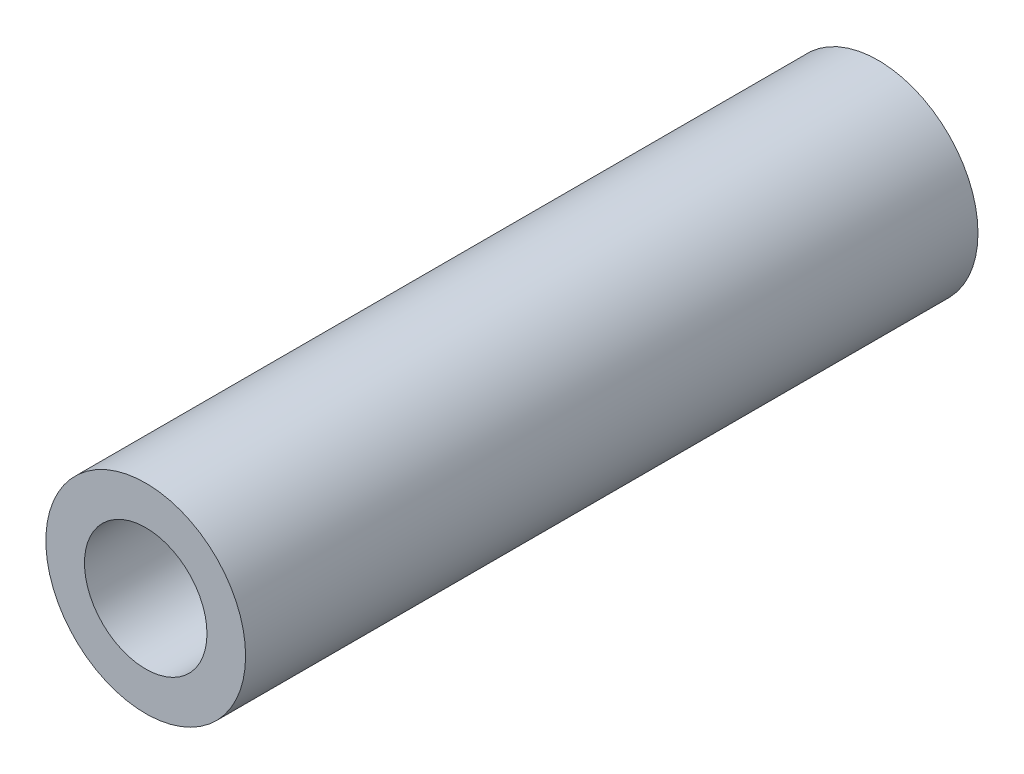
SolidWorks part; units mm, degrees
ref_plane "Front Plane" through (0, 0, 0) normal (0, 0, 1) x (1, 0, 0)
ref_plane "Top Plane" through (0, 0, 0) normal (0, 1, 0) x (1, 0, 0)
ref_plane "Right Plane" through (0, 0, 0) normal (1, 0, 0) x (0, 0, -1)
sketch "Sketch1" plane through (0, 0, 0) normal (1, 0, 0) x (0, 0, -1)
  line L0 (-8.7312, -1.4605) -> (-8.7312, 1.4605) construction
  line L1 (8.7312, -2.3813) -> (-8.7312, -2.3813) construction
  line L2 (8.7312, -2.3813) -> (8.7312, 2.3813) construction
  line L3 (8.7312, 2.3813) -> (-8.7312, 2.3813) construction
  line L4 (-8.7312, -2.3813) -> (-8.7312, 2.3813) construction
  line L5 (0, 2.3812) -> (0, -2.3812) construction
  line L6 (8.7312, 0) -> (-8.7312, 0) construction
  point P0 (0, 0)
  point P7 (-8.7312, 0)
  dimension "D1" = 2.921
  dimension "D2" = 4.7625
sketch "Sketch3" plane through (0, 0, 0) normal (0, 0, 1) x (1, 0, 0)
  circle A0 centre (0, 0) radius 1.4605 construction
  circle A1 centre (0, 0) radius 2.3813 construction
  point P6 (0, -1.4605)
  dimension "OD" = 4.7625
  dimension "ID" = 2.921
sketch "Sketch2" plane through (0, 0, 0) normal (0, 0, 1) x (1, 0, 0)
  circle A0 centre (0, 0) radius 2.3812
  circle A1 centre (0, 0) radius 1.4605
extrude "Extrude1" add sketch "Sketch2" along normal up to vertex and the other way up to vertex up to point (0, -2.3813, 8.7312) other way up to point (0, 2.3813, -8.7312)
equation "\"D1@Sketch1\"=\"ID@Sketch3\""
equation "\"D2@Sketch1\"=\"OD@Sketch3\""
